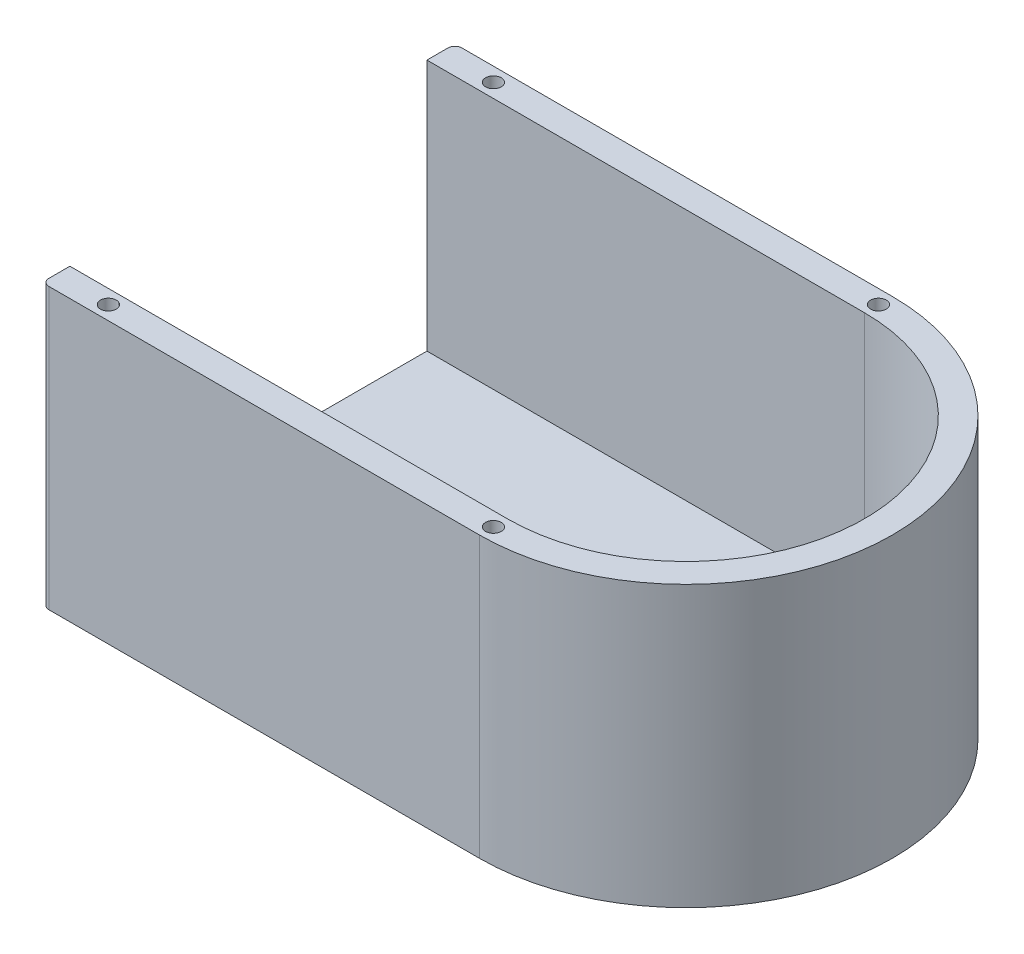
SolidWorks part; units mm, degrees
material "Custom Plastic"
ref_plane "Front Plane" through (0, 0, 0) normal (0, 0, 1) x (1, 0, 0)
ref_plane "Top Plane" through (0, 0, 0) normal (0, 1, 0) x (1, 0, 0)
ref_plane "Right Plane" through (0, 0, 0) normal (1, 0, 0) x (0, 0, -1)
sketch "Sketch2" plane through (0, 0, 0) normal (0, 1, 0) x (1, 0, 0)
  line L6 (0, 0) -> (-137.3228, 0) construction
  line L8 (-125, 59) -> (0, 59)
  line L9 (-125, 59) -> (-125, -59)
  line L10 (-125, -59) -> (0, -59)
  arc A1 (0, -59) -> (0, 59) centre (0, 0) ccw
  dimension "D3" = 118
  dimension "D1" = 118
  dimension "D2" = 125
extrude "BottomExtrude" add sketch "Sketch2" along normal blind 80
shell "Shell1" thickness 8 removed face at (-47.75, 80, 0)
sketch "Sketch3" plane through (0, 0, 0) normal (1, 0, 0) x (0, 0, -1)
  line L0 (51, 8) -> (-51, 8) construction
  line L1 (51, 80) -> (-51, 80) construction
  line L2 (51, 80) -> (51, 8) construction
  line L3 (-51, 80) -> (-51, 8) construction
  line L4 (51, 8) -> (-51, 8)
  line L5 (51, 80) -> (-51, 80)
  line L6 (51, 80) -> (51, 8)
  line L7 (-51, 80) -> (-51, 8)
extrude "Cut-Extrude1" cut sketch "Sketch3" against normal through all
sketch "Sketch4" plane through (-125, 0, 0) normal (-1, 0, 0) x (0, 0, 1)
  line L0 (-59, 70) -> (-51, 70) construction
  line L1 (-59, 80) -> (-59, 0) construction
  line L2 (-51, 80) -> (-51, 8) construction
  line L3 (-59, 80) -> (-51, 80) construction
  line L4 (-59, 5) -> (59, 5) construction
  line L5 (59, 80) -> (59, 0) construction
  line L6 (-59, 0) -> (59, 0) construction
  circle A0 centre (-55, 70) radius 2.25
  circle A1 centre (55, 70) radius 2.25
  circle A2 centre (55, 5) radius 2.25
  circle A3 centre (-55, 5) radius 2.25
  point P17 (-55, 70)
  dimension "D1" = 4.5
  dimension "D2" = 4.5
  dimension "D3" = 4.5
  dimension "D4" = 4.5
  dimension "D5" = 10
  dimension "D6" = 5
  dimension "D7" = 4
extrude "Cut-Extrude2" cut sketch "Sketch4" against normal blind 6
sketch "Sketch5" plane through (0, 80, 0) normal (0, 1, 0) x (1, 0, 0)
  line L0 (0, 59) -> (-125, 59) construction
  line L1 (-125, -59) -> (0, -59) construction
  line L2 (-125, 59) -> (-125, 51) construction
  circle A0 centre (0, 55) radius 2.25
  circle A1 centre (-110, 55) radius 2.25
  circle A2 centre (-110, -55) radius 2.25
  circle A3 centre (0, -55) radius 2.25
  dimension "D1" = 4.5
  dimension "D2" = 4.5
  dimension "D3" = 4.5
  dimension "D4" = 4.5
  dimension "D5" = 4
  dimension "D6" = 4
  dimension "D7" = 15
extrude "Cut-Extrude3" cut sketch "Sketch5" against normal blind 6
fillet "Fillet2" radius 2 1 edges at (-125, 40, -59)
fillet "Fillet3" radius 2 1 edges at (-125, 40, 59)
equation "\"Hole\"= 8mm"
